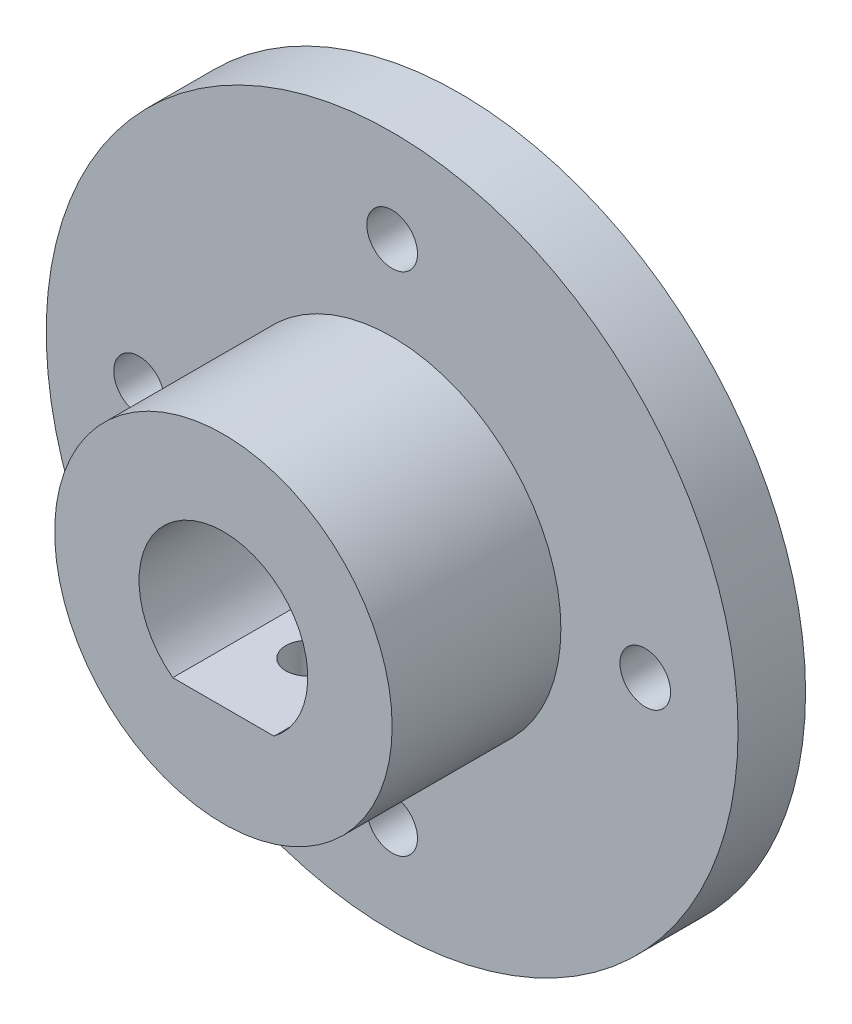
SolidWorks part; units mm, degrees
ref_plane "前视基准面" through (0, 0, 0) normal (0, 0, 1) x (1, 0, 0)
ref_plane "上视基准面" through (0, 0, 0) normal (0, 1, 0) x (1, 0, 0)
ref_plane "右视基准面" through (0, 0, 0) normal (1, 0, 0) x (0, 0, -1)
sketch "草图1" plane through (0, 0, 0) normal (0, 0, 1) x (1, 0, 0)
  line L0 (-3, -4) -> (3, -4)
  arc A0 (1.5, 15) -> (-1.5, 15) centre (0, 15) ccw construction
  arc A1 (-1.5, 15) -> (1.5, 15) centre (0, 15) ccw construction
  arc A2 (-20.5, 0) -> (20.5, 0) centre (0, 0) ccw
  arc A3 (20.5, 0) -> (-20.5, 0) centre (0, 0) ccw
  arc A4 (-20.5, 0) -> (20.5, 0) centre (0, 0) ccw
  arc A5 (20.5, 0) -> (-20.5, 0) centre (0, 0) ccw
  arc A6 (16.5, 0) -> (13.5, 0) centre (15, 0) ccw construction
  arc A7 (13.5, 0) -> (16.5, 0) centre (15, 0) ccw construction
  arc A8 (1.5, -15) -> (-1.5, -15) centre (0, -15) ccw construction
  arc A9 (-1.5, -15) -> (1.5, -15) centre (0, -15) ccw construction
  arc A10 (-13.5, 0) -> (-16.5, 0) centre (-15, 0) ccw construction
  arc A11 (-16.5, 0) -> (-13.5, 0) centre (-15, 0) ccw construction
  arc A12 (-16.5, 0) -> (-13.5, 0) centre (-15, 0) ccw
  arc A13 (-13.5, 0) -> (-16.5, 0) centre (-15, 0) ccw
  arc A14 (-1.5, -15) -> (1.5, -15) centre (0, -15) ccw
  arc A15 (1.5, -15) -> (-1.5, -15) centre (0, -15) ccw
  arc A16 (13.5, 0) -> (16.5, 0) centre (15, 0) ccw
  arc A17 (16.5, 0) -> (13.5, 0) centre (15, 0) ccw
  arc A18 (-1.5, 15) -> (1.5, 15) centre (0, 15) ccw
  arc A19 (1.5, 15) -> (-1.5, 15) centre (0, 15) ccw
  arc A20 (-5, 0) -> (5, 0) centre (0, 0) ccw construction
  arc A21 (5, 0) -> (-5, 0) centre (0, 0) ccw construction
  arc A22 (-5, 0) -> (-3, -4) centre (0, 0) ccw
  arc A23 (5, 0) -> (-5, 0) centre (0, 0) ccw
  arc A24 (3, -4) -> (5, 0) centre (0, 0) ccw
  dimension "D2" = 4
  dimension "D1" = 0
extrude "凸台-拉伸1" add sketch "草图1" along normal blind 4
sketch "草图2" plane through (0, 0, 4) normal (0, 0, 1) x (1, 0, 0)
  line L0 (-3, -4) -> (3, -4)
  arc A0 (3, -4) -> (-3, -4) centre (0, 0) ccw
  circle A1 centre (0, 0) radius 10
  point P6 (3, 4)
  dimension "D1" = 20
  dimension "D3" = 10
  dimension "D2" = 4
extrude "凸台-拉伸2" add sketch "草图2" along normal blind 10
sketch "草图3" plane through (0, 0, 0) normal (0, 1, 0) x (1, 0, 0)
  line L0 (0, -9) -> (0, 0) construction
  circle A0 centre (0, -9) radius 1.3
  dimension "D2" = 2.6
  dimension "D1" = 9
extrude "切除-拉伸1" cut sketch "草图3" against normal blind 13
